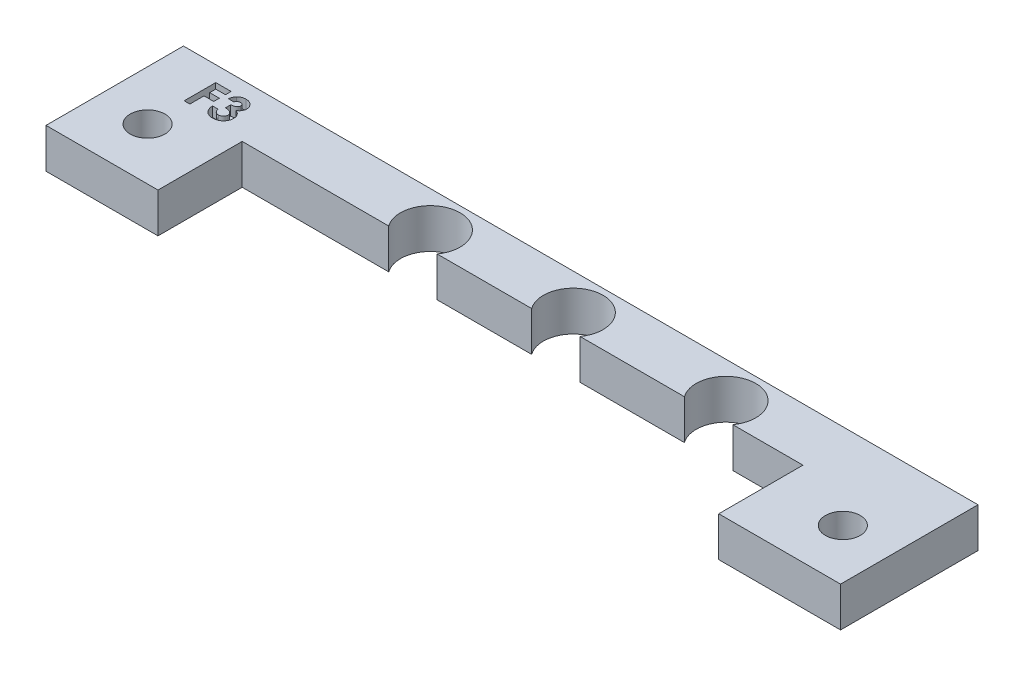
SolidWorks part; units mm, degrees
ref_plane "Front Plane" through (0, 0, 0) normal (0, 0, 1) x (1, 0, 0)
ref_plane "Top Plane" through (0, 0, 0) normal (0, 1, 0) x (1, 0, 0)
ref_plane "Right Plane" through (0, 0, 0) normal (1, 0, 0) x (0, 0, -1)
sketch "Sketch1" plane through (0, 0, 0) normal (0, 1, 0) x (1, 0, 0)
  line L0 (-8.8602, -26.3374) -> (-20.1352, -26.3374)
  line L1 (-20.1352, -26.3374) -> (-20.1352, -0.8374)
  line L2 (-20.1352, -0.8374) -> (-1.1702, -0.8374)
  line L3 (47.5998, -0.8374) -> (59.8648, -0.8374)
  line L4 (59.8648, -0.8374) -> (59.8648, -26.3374)
  line L5 (59.8648, -26.3374) -> (39.9098, -26.3374)
  line L6 (-5.1102, -25.3374) -> (36.1598, -25.3374)
  line L7 (-15.1352, -0.8374) -> (-15.1352, -26.3374) construction
  line L8 (54.8648, -26.3374) -> (54.8648, -0.8374) construction
  line L9 (2.5798, -0.8374) -> (43.8498, -0.8374)
  line L10 (-20.1352, -10.3374) -> (59.8648, -10.3374) construction
  line L11 (-15.1352, -10.3374) -> (-15.1352, -0.8374)
  line L12 (-20.1352, -18.8163) -> (59.8648, -18.8163)
  line L13 (3.6398, -18.5874) -> (3.6398, -0.8374) construction
  line L14 (3.6398, -0.8374) -> (5.5698, -0.8374) construction
  line L15 (-5.1102, -26.3374) -> (39.9098, -26.3374)
  line L16 (-20.1352, -4.9779) -> (59.8648, -4.9779)
  line L17 (-20.1352, -10.3374) -> (59.8648, -10.3374)
  line L18 (47.5998, -16.8374) -> (47.5998, -26.3374)
  circle A0 centre (-15.1352, -13.5874) radius 1.75
  circle A1 centre (54.8648, -13.5874) radius 1.75
  line B0 (-1.1702, -0.8374) -> (-1.1702, -16.8374)
  line B1 (-1.1702, -16.8374) -> (17.8298, -16.8374)
  line B2 (17.8298, -16.8374) -> (17.8298, -0.8374)
  line B3 (17.8298, -0.8374) -> (14.0798, -0.8374)
  line B4 (14.0798, -0.8374) -> (14.0798, -1.8374)
  line B5 (14.0798, -1.8374) -> (16.0798, -1.8374)
  line B6 (16.0798, -1.8374) -> (16.0798, -15.3374)
  line B7 (16.0798, -15.3374) -> (0.5798, -15.3374)
  line B8 (0.5798, -15.3374) -> (0.5798, -1.8374)
  line B9 (0.5798, -1.8374) -> (2.5798, -1.8374)
  line B10 (2.5798, -1.8374) -> (2.5798, -0.8374)
  line B11 (2.5798, -0.8374) -> (-1.1702, -0.8374)
  line B12 (0.5798, -1.8374) -> (16.0798, -15.3374) construction
  line B13 (0.5798, -15.3374) -> (16.0798, -1.8374) construction
  line B14 (0.5798, -8.5874) -> (16.0798, -8.5874) construction
  line B15 (2.5798, -1.8374) -> (14.0798, -1.8374) construction
  line B16 (8.3298, -1.8374) -> (8.3298, -15.3374) construction
  circle B17 centre (8.3298, -8.5874) radius 3
  line B18 (10.1398, -26.3374) -> (10.1398, -10.3374)
  line B19 (10.1398, -10.3374) -> (-8.8602, -10.3374)
  line B20 (-8.8602, -10.3374) -> (-8.8602, -26.3374)
  line B21 (-8.8602, -26.3374) -> (-5.1102, -26.3374)
  line B22 (-5.1102, -26.3374) -> (-5.1102, -25.3374)
  line B23 (-5.1102, -25.3374) -> (-7.1102, -25.3374)
  line B24 (-7.1102, -25.3374) -> (-7.1102, -11.8374)
  line B25 (-7.1102, -11.8374) -> (8.3898, -11.8374)
  line B26 (8.3898, -11.8374) -> (8.3898, -25.3374)
  line B27 (8.3898, -25.3374) -> (6.3898, -25.3374)
  line B28 (6.3898, -25.3374) -> (6.3898, -26.3374)
  line B29 (6.3898, -26.3374) -> (10.1398, -26.3374)
  line B30 (8.3898, -25.3374) -> (-7.1102, -11.8374) construction
  line B31 (8.3898, -11.8374) -> (-7.1102, -25.3374) construction
  line B32 (8.3898, -18.5874) -> (-7.1102, -18.5874) construction
  line B33 (6.3898, -25.3374) -> (-5.1102, -25.3374) construction
  line B34 (0.6398, -25.3374) -> (0.6398, -11.8374) construction
  circle B35 centre (0.6398, -18.5874) radius 3
  line B36 (28.5998, -0.8374) -> (28.5998, -16.8374)
  line B37 (28.5998, -16.8374) -> (47.5998, -16.8374)
  line B38 (47.5998, -16.8374) -> (47.5998, -0.8374)
  line B39 (47.5998, -0.8374) -> (43.8498, -0.8374)
  line B40 (43.8498, -0.8374) -> (43.8498, -1.8374)
  line B41 (43.8498, -1.8374) -> (45.8498, -1.8374)
  line B42 (45.8498, -1.8374) -> (45.8498, -15.3374)
  line B43 (45.8498, -15.3374) -> (30.3498, -15.3374)
  line B44 (30.3498, -15.3374) -> (30.3498, -1.8374)
  line B45 (30.3498, -1.8374) -> (32.3498, -1.8374)
  line B46 (32.3498, -1.8374) -> (32.3498, -0.8374)
  line B47 (32.3498, -0.8374) -> (28.5998, -0.8374)
  line B48 (30.3498, -1.8374) -> (45.8498, -15.3374) construction
  line B49 (30.3498, -15.3374) -> (45.8498, -1.8374) construction
  line B50 (30.3498, -8.5874) -> (45.8498, -8.5874) construction
  line B51 (32.3498, -1.8374) -> (43.8498, -1.8374) construction
  line B52 (38.0998, -1.8374) -> (38.0998, -15.3374) construction
  circle B53 centre (38.0998, -8.5874) radius 3
  line B54 (13.2198, -0.8374) -> (13.2198, -16.8374)
  line B55 (13.2198, -16.8374) -> (32.2198, -16.8374)
  line B56 (32.2198, -16.8374) -> (32.2198, -0.8374)
  line B57 (32.2198, -0.8374) -> (28.4698, -0.8374)
  line B58 (28.4698, -0.8374) -> (28.4698, -1.8374)
  line B59 (28.4698, -1.8374) -> (30.4698, -1.8374)
  line B60 (30.4698, -1.8374) -> (30.4698, -15.3374)
  line B61 (30.4698, -15.3374) -> (14.9698, -15.3374)
  line B62 (14.9698, -15.3374) -> (14.9698, -1.8374)
  line B63 (14.9698, -1.8374) -> (16.9698, -1.8374)
  line B64 (16.9698, -1.8374) -> (16.9698, -0.8374)
  line B65 (16.9698, -0.8374) -> (13.2198, -0.8374)
  line B66 (14.9698, -1.8374) -> (30.4698, -15.3374) construction
  line B67 (14.9698, -15.3374) -> (30.4698, -1.8374) construction
  line B68 (14.9698, -8.5874) -> (30.4698, -8.5874) construction
  line B69 (16.9698, -1.8374) -> (28.4698, -1.8374) construction
  line B70 (22.7198, -1.8374) -> (22.7198, -15.3374) construction
  circle B71 centre (22.7198, -8.5874) radius 3
  line B72 (39.9098, -26.3374) -> (39.9098, -10.3374)
  line B73 (39.9098, -10.3374) -> (20.9098, -10.3374)
  line B74 (20.9098, -10.3374) -> (20.9098, -26.3374)
  line B75 (20.9098, -26.3374) -> (24.6598, -26.3374)
  line B76 (24.6598, -26.3374) -> (24.6598, -25.3374)
  line B77 (24.6598, -25.3374) -> (22.6598, -25.3374)
  line B78 (22.6598, -25.3374) -> (22.6598, -11.8374)
  line B79 (22.6598, -11.8374) -> (38.1598, -11.8374)
  line B80 (38.1598, -11.8374) -> (38.1598, -25.3374)
  line B81 (38.1598, -25.3374) -> (36.1598, -25.3374)
  line B82 (36.1598, -25.3374) -> (36.1598, -26.3374)
  line B83 (36.1598, -26.3374) -> (39.9098, -26.3374)
  line B84 (38.1598, -25.3374) -> (22.6598, -11.8374) construction
  line B85 (38.1598, -11.8374) -> (22.6598, -25.3374) construction
  line B86 (38.1598, -18.5874) -> (22.6598, -18.5874) construction
  line B87 (36.1598, -25.3374) -> (24.6598, -25.3374) construction
  line B88 (30.4098, -25.3374) -> (30.4098, -11.8374) construction
  circle B89 centre (30.4098, -18.5874) radius 3
  line B90 (24.5298, -26.3374) -> (24.5298, -10.3374)
  line B91 (24.5298, -10.3374) -> (5.5298, -10.3374)
  line B92 (5.5298, -10.3374) -> (5.5298, -26.3374)
  line B93 (5.5298, -26.3374) -> (9.2798, -26.3374)
  line B94 (9.2798, -26.3374) -> (9.2798, -25.3374)
  line B95 (9.2798, -25.3374) -> (7.2798, -25.3374)
  line B96 (7.2798, -25.3374) -> (7.2798, -11.8374)
  line B97 (7.2798, -11.8374) -> (22.7798, -11.8374)
  line B98 (22.7798, -11.8374) -> (22.7798, -25.3374)
  line B99 (22.7798, -25.3374) -> (20.7798, -25.3374)
  line B100 (20.7798, -25.3374) -> (20.7798, -26.3374)
  line B101 (20.7798, -26.3374) -> (24.5298, -26.3374)
  line B102 (22.7798, -25.3374) -> (7.2798, -11.8374) construction
  line B103 (22.7798, -11.8374) -> (7.2798, -25.3374) construction
  line B104 (22.7798, -18.5874) -> (7.2798, -18.5874) construction
  line B105 (20.7798, -25.3374) -> (9.2798, -25.3374) construction
  line B106 (15.0298, -25.3374) -> (15.0298, -11.8374) construction
  circle B107 centre (15.0298, -18.5874) radius 3
  dimension "D1" = 80
  dimension "D2" = 25.5
  dimension "D3" = 5
  dimension "D4" = 5
  dimension "D5" = 7.69
  dimension "D6" = 11.275
  dimension "D7" = 7.69
  dimension "D8" = 6.7
  dimension "D9" = 7.69
  dimension "D10" = 7.69
  dimension "D11" = 12.265
sketch_block_instance "Block1-1"
sketch_block "Block1" parameters "D1"=13, "D2"=15, "D3"=2, "D4"=1.75, "D5"=2, "D6"=2, "D7"=2, "D8"=2, "D9"=13.0756, "D10"=17, "D11"=17, "D12"=18.7479, "D13"=13, "D14"=2
sketch_block_instance "Block1-2"
sketch_block_instance "Block1-3"
sketch_block_instance "Block1-4"
sketch_block_instance "Block1-5"
sketch_block_instance "Block1-6"
extrude "Boss-Extrude1" add sketch "Sketch1" along normal blind 4 contours B20 L17 L1 L12 A0 | B0 L16 L11 L17 | L1 L17 L11 L16 | L17 B8 L16 B0 | B54 L16 B8 L17 B17 | L16 B54 L17 B6 | L16 B6 L17 B2 | B71 L17 B36 L16 B2 | L17 B44 L16 B36 | L17 B56 L16 B44 | B56 L17 B53 B42 L16 | L16 B42 L17 B38 | B38 L17 L4 L16 | B72 L12 L4 L17 B38 B37 A1 | B62 L17 B6 L16 | B60 L16 B44 L17 region at (-14.4977, 0, 18.6752) region at (-8.1527, 0, 7.6577) region at (-17.6352, 0, 7.6577) region at (-0.2952, 0, 7.6577) region at (0.7171, 0, 7.6577) region at (14.0948, 0, 7.6577) region at (15.5248, 0, 7.6577) region at (16.9548, 0, 7.6577) region at (23.2148, 0, 5.0982) region at (29.4748, 0, 7.6577) region at (30.4098, 0, 7.6577) region at (31.3448, 0, 7.6577) region at (39.0348, 0, 5.1244) region at (47.7489, 0, 17.8269) region at (46.7248, 0, 7.6577) region at (53.7323, 0, 7.6577)
sketch "Sketch2" plane through (0, 4, 0) normal (0, 1, 0) x (1, 0, 0)
  text T0 "<b>F3</b>"
extrude "Cut-Extrude1" cut sketch "Sketch2" against normal blind 1
